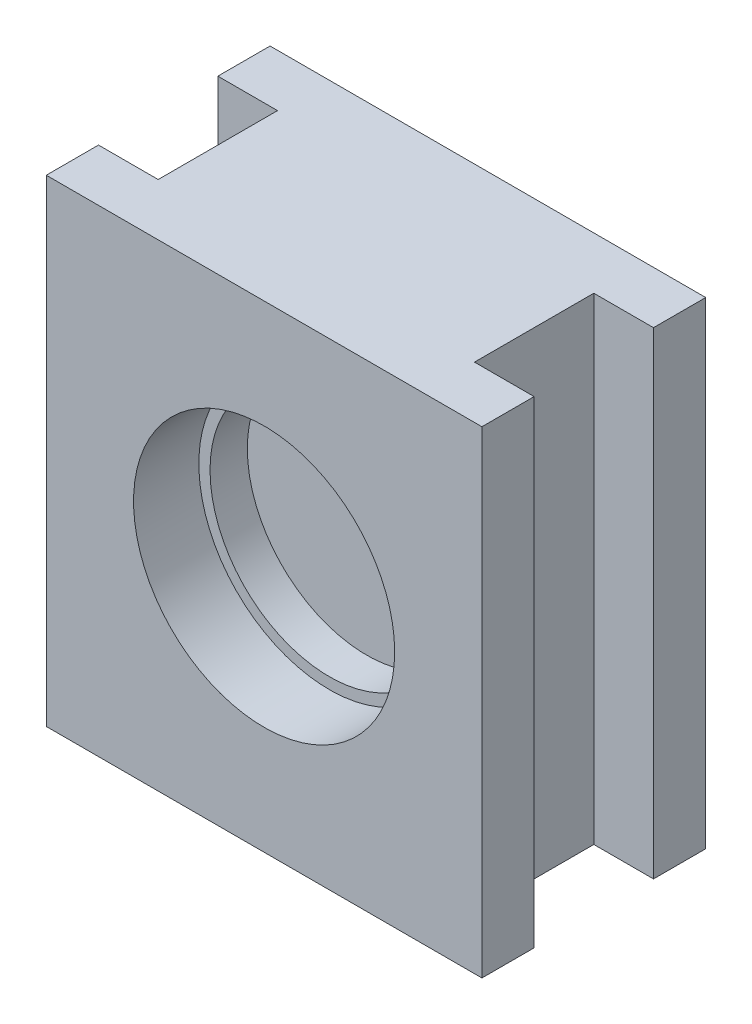
SolidWorks part; units mm, degrees
material "Gray Cast Iron (SN)"
ref_plane "Front Plane" through (0, 0, 0) normal (0, 0, 1) x (1, 0, 0)
ref_plane "Top Plane" through (0, 0, 0) normal (0, 1, 0) x (1, 0, 0)
ref_plane "Right Plane" through (0, 0, 0) normal (1, 0, 0) x (0, 0, -1)
sketch "Sketch1" plane through (0, 0, 0) normal (0, 0, 1) x (1, 0, 0)
  line L1 (13.462, 20.32) -> (-13.462, 20.32)
  line L2 (13.462, 20.32) -> (13.462, -20.32)
  line L3 (13.462, -20.32) -> (-13.462, -20.32)
  line L4 (-13.462, 20.32) -> (-13.462, -20.32)
  line L5 (13.462, 20.32) -> (-13.462, -20.32) construction
  line L6 (13.462, -20.32) -> (-13.462, 20.32) construction
  point P0 (0, 0)
  dimension "D1" = 26.924
  dimension "D2" = 40.64
extrude "Boss-Extrude1" add sketch "Sketch1" along normal blind 19.05
sketch "Sketch2" plane through (13.462, 0, 0) normal (1, 0, 0) x (0, 0, -1)
  line L0 (-19.05, -20.32) -> (0, -20.32) construction
  line L1 (-14.605, -20.32) -> (-4.445, -20.32)
  line L2 (-14.605, -20.32) -> (-14.605, 20.32)
  line L3 (-14.605, 20.32) -> (-4.445, 20.32)
  line L4 (-4.445, -20.32) -> (-4.445, 20.32)
  line L5 (-19.05, 20.32) -> (0, 20.32) construction
  line L6 (-9.525, 20.32) -> (-9.525, -20.32) construction
  line M1 (0, -20.32) -> (0, 20.32)
  line M2 (0, 20.32) -> (-19.05, 20.32)
  line M3 (-19.05, 20.32) -> (-19.05, -20.32)
  line M4 (-19.05, -20.32) -> (0, -20.32)
  dimension "D1" = 10.16
extrude "Boss-Extrude2" add sketch "Sketch2" along normal blind 5.08 contours L2 M4 M2 M3 | L4 M4 M1 M2 region at (13.462, 0, 16.8275) region at (13.462, 0, 2.2225)
mirror "Mirror1" about plane through (0, 0, 0) normal (1, 0, 0) of "Boss-Extrude2"
scale "Scale1" [suppressed]
sketch "Sketch3" plane through (0, 0, 19.05) normal (0, 0, 1) x (1, 0, 0)
  circle A0 centre (0, 0) radius 11.1125
  dimension "D1" = 22.225
extrude "Cut-Extrude1" cut sketch "Sketch3" against normal blind 5.5562
sketch "Sketch4" plane through (0, 0, 13.4938) normal (0, 0, 1) x (1, 0, 0)
  circle A0 centre (0, 0) radius 10.16
  dimension "D1" = 20.32
extrude "Cut-Extrude2" cut sketch "Sketch4" against normal blind 3.175
